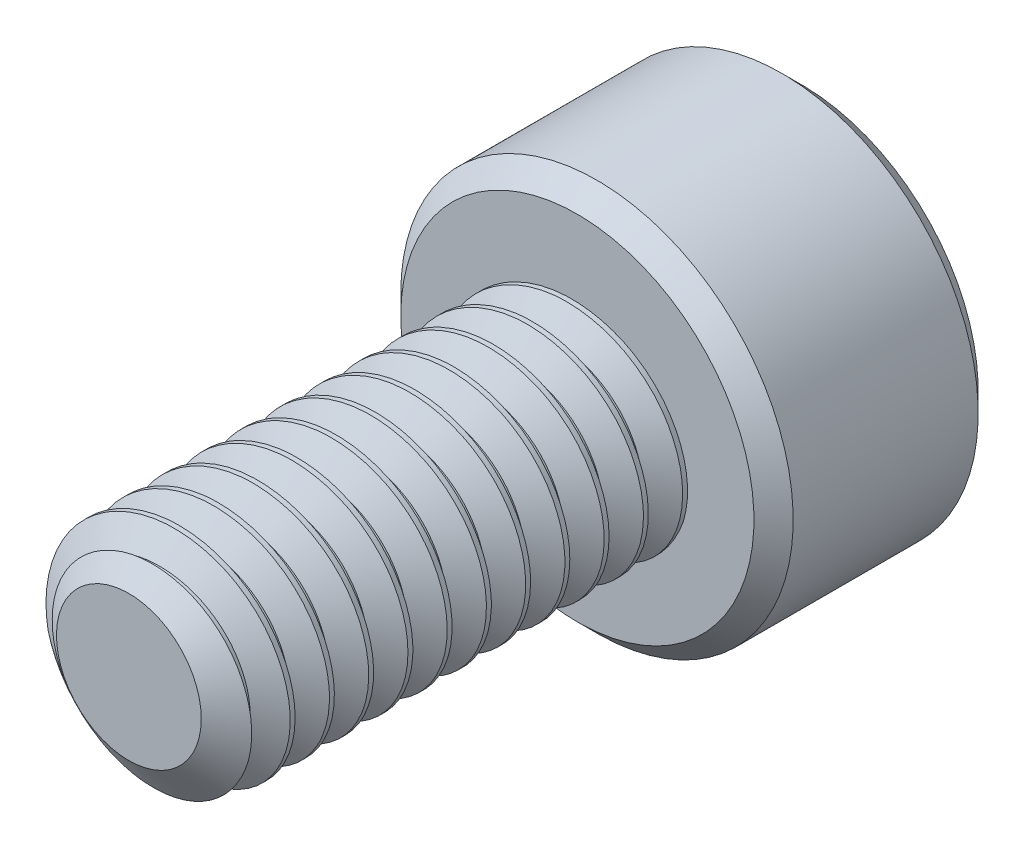
SolidWorks part; units mm, degrees
other "DetailItem1"
ref_plane "Front Plane" through (0, 0, 0) normal (0, 0, 1) x (1, 0, 0)
ref_plane "Top Plane" through (0, 0, 0) normal (0, 1, 0) x (1, 0, 0)
ref_plane "Right Plane" through (0, 0, 0) normal (1, 0, 0) x (0, 0, -1)
sketch "Sketch1" plane through (0, 0, 0) normal (0, 0, 1) x (1, 0, 0)
  circle A0 centre (0, 0) radius 2
  dimension "OD" = 4
extrude "Extrude1" add sketch "Sketch1" against normal blind 8
sketch "Sketch2" plane through (0, 0, 0) normal (0, 0, 1) x (1, 0, 0)
  circle A0 centre (0, 0) radius 2 construction
  circle A1 centre (0, 0) radius 2
curve "Helix/Spiral1" pitch 0.7 height 8.7 radius 2 centre (0, 0, 0) axis (0, 0, -1) start towards (0, 1, 0) parameters "pitch"=0.7
sketch "Sketch3" plane through (0, 0, 0) normal (1, 0, 0) x (0, 0, -1)
  line L0 (-0.6125, 2) -> (-0.35, 1.5453)
  line L1 (-0.35, 1.5453) -> (-0.2625, 1.5453)
  line L2 (-0.2625, 1.5453) -> (0, 2)
  line L3 (-0.6125, 2) -> (0, 2)
  line L4 (-0.3062, 2) -> (-0.3062, 1.5453) construction
  line L5 (-0.4812, 1.7727) -> (-0.1312, 1.7727) construction
  line L6 (0, 2) -> (0, -2) construction
  dimension "D1" = 0.0875
  dimension "D2" = 0.35
  dimension "D3" = 60
sweep "Cut-Sweep1" cut profiles "Sketch3" path "Helix/Spiral1" align with end faces yes
sketch "Sketch4" plane through (0, 0, 0) normal (1, 0, 0) x (0, 0, -1)
  line L0 (0.4962, 2) -> (0, 1.2913)
  line L1 (0, 1.2913) -> (0, 2)
  line L2 (0.4962, 2) -> (0, 2)
  line L3 (-0.6125, 2) -> (0, 2) construction
  line L4 (0, 0) -> (7.0209, 0) construction
  dimension "D1" = 55
  dimension "D2" = 0.254
revolve "Cut-Revolve1" cut sketch "Sketch4" angle 360 about L4
sketch "Sketch6" plane through (0, 0, -8) normal (0, 0, -1) x (-1, 0, 0)
  circle A0 centre (0, 0) radius 3.5
  dimension "head dia" = 7
extrude "Extrude2" add sketch "Sketch6" along normal blind 4
sketch "Sketch7" plane through (0, 0, -12) normal (0, 0, -1) x (-1, 0, 0)
  line L1 (0, 1.7321) -> (-1.5, 0.866)
  line L2 (-1.5, 0.866) -> (-1.5, -0.866)
  line L3 (-1.5, -0.866) -> (0, -1.7321)
  line L4 (0, -1.7321) -> (1.5, -0.866)
  line L5 (1.5, -0.866) -> (1.5, 0.866)
  line L6 (1.5, 0.866) -> (0, 1.7321)
  circle A0 centre (0, 0) radius 1.5 construction
  dimension "hex dia" = 3
extrude "Cut-Extrude1" cut sketch "Sketch7" against normal blind 2.25
sketch "Sketch8" plane through (0, 0, -12) normal (0, 0, -1) x (-1, 0, 0)
  circle A0 centre (0, 0) radius 1.7321
extrude "Cut-Extrude2" cut sketch "Sketch8" against normal through all draft 45
chamfer "Chamfer1" distance 0.35 angle 45 2 edges at (-3.5, 0, -12) (-3.5, 0, -8)
sketch "Sketch10" plane through (0, 0, -8) normal (0, 0, 1) x (1, 0, 0)
  circle A1 centre (0, 0) radius 2
  circle A2 centre (0, 0) radius 2
  dimension "D1" = 0
ref_plane "Plane1" through (0, 0, 0) normal (0, 0, 1) x (1, 0, 0)
extrude "partial thread" [suppressed] add sketch "Sketch10" along normal up to surface (10 mm away) separate body up to plane "Plane1"
chamfer "Chamfer2" [suppressed] distance 0.08 angle 45
combine bodies "Combine1" [suppressed] operation type add bodies to combine 107 108
sketch "Sketch9" plane through (0, 0, 0) normal (1, 0, 0) x (0, 0, -1)
  line L0 (0, 2) -> (0, -2) construction
  line L1 (1.75, 2) -> (1.75, -2) construction
  dimension "D1" = 1.75
equation "\"D3@Helix/Spiral1\" = \"screw length@Extrude1\"+\"pitch@Helix/Spiral1\""
equation "\"D1@Sketch3\" = \"pitch@Helix/Spiral1\"*.125"
equation "\"D2@Sketch3\" = \"pitch@Helix/Spiral1\"*.5"
equation "\"D1@Cut-Extrude1\" = \"hex dia@Sketch7\"*.75"
equation "\"D1@Chamfer1\" = \"head dia@Sketch6\"*.05"
equation "\"D1@Sketch9\" = \"pitch@Helix/Spiral1\"*2.5"
equation "\"D1@Chamfer2\"=\"OD@Sketch1\"*.02"
